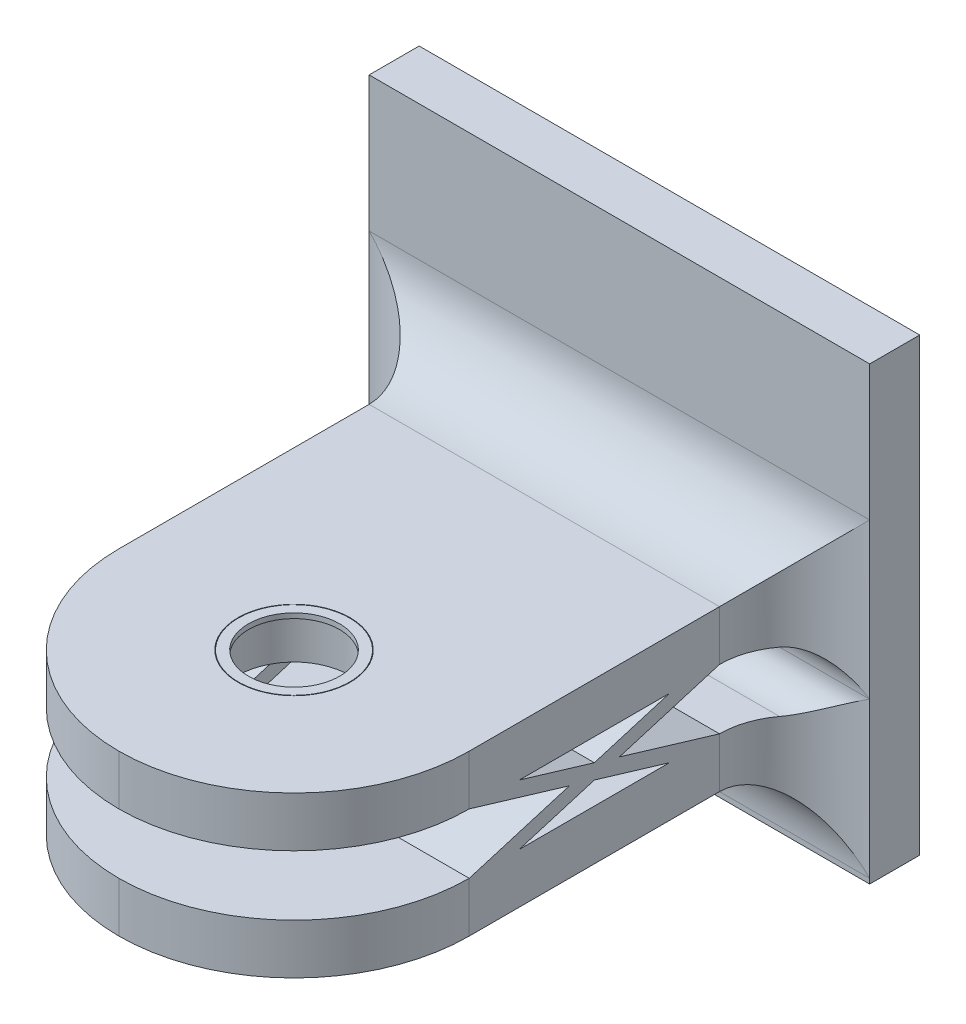
SolidWorks part; units mm, degrees
ref_plane "Plan de face" through (0, 0, 0) normal (1, 0, 0) x (0, 1, 0)
ref_plane "Plan de dessus" through (0, 0, 0) normal (0, 0, 1) x (0, 1, 0)
ref_plane "Plan de droite" through (0, 0, 0) normal (0, 1, 0) x (-1, 0, 0)
sketch "Esquisse1" plane through (0, 0, 0) normal (0, 0, 1) x (0, 1, 0)
  line L1 (0, 0) -> (90, 0)
  line L2 (0, 0) -> (0, 100)
  line L3 (0, 100) -> (90, 100)
  line L4 (90, 0) -> (90, 100)
  dimension "D1" = 90
  dimension "D2" = 100
extrude "Boss.-Extru.1" add sketch "Esquisse1" along normal blind 10
sketch "Esquisse2" plane through (0, 0, 10) normal (0, 0, 1) x (1, 0, 0)
  line L6 (0, 0) -> (0, 90) construction
  line L8 (-85, 48) -> (-15, 48)
  line L9 (-85, 48) -> (-85, 38)
  line L10 (-85, 38) -> (-15, 38)
  line L11 (-15, 48) -> (-15, 38)
  line L16 (-85, 26) -> (-15, 26)
  line L17 (-85, 26) -> (-85, 16)
  line L18 (-85, 16) -> (-15, 16)
  line L19 (-15, 26) -> (-15, 16)
  dimension "D2" = 10
  dimension "D6" = 70
  dimension "D7" = 15
  dimension "D12" = 70
  dimension "D13" = 10
  dimension "D14" = 12
extrude "Boss.-Extru.2" add sketch "Esquisse2" along normal blind 100
fillet "Congé1" radius 35 4 edges at (-15, 43, 110) (-85, 43, 110) (-15, 21, 110) (-85, 21, 110)
sketch "Esquisse3" plane through (0, 90, 0) normal (0, 1, 0) x (-1, 0, 0)
  line L0 (0, 10) -> (0, 0) construction
  line L2 (0, 0) -> (100, 0) construction
  circle A0 centre (50, 75) radius 11.2
  dimension "D3" = 22.4
  dimension "D1" = 50
  dimension "D2" = 75
extrude "Enlèv. mat.-Extru.1" cut sketch "Esquisse3" against normal blind 208
fillet "Congé2" radius 15 6 edges at (-15, 43, 10) (-50, 48, 10) (-85, 43, 10) (-85, 21, 10) (-15, 21, 10) (-50, 16, 10)
ref_axis "Axe2" through (-50, 16, 110) along (0, 0, -1)
sketch "Esquisse10" plane through (0, 48, 0) normal (0, 1, 0) x (-1, 0, 0)
  circle A0 centre (50, 75) radius 11.0955
  circle A1 centre (50, 75) radius 9.0955
  dimension "D1" = 2
extrude "Boss.-Extru.7" add sketch "Esquisse10" against normal blind 1 separate body
fillet "Congé7" radius 6 2 edges at (-50, 26, 10) (-50, 38, 10)
sketch "Esquisse15" plane through (0, 26, 0) normal (0, 1, 0) x (-1, 0, 0)
  circle A0 centre (50, 75) radius 11.0955
  circle A1 centre (50, 75) radius 9.0955
extrude "Boss.-Extru.11" add sketch "Esquisse15" against normal blind 0.5 separate body
sketch "Esquisse16" plane through (-15, 0, 0) normal (1, 0, 0) x (0, 1, 0)
  line L0 (26, 25) -> (26, 35)
  line L1 (26, 25) -> (38, 65)
  line L2 (26, 35) -> (38, 75)
  line L3 (38, 65) -> (38, 75)
  line L4 (26, 75) -> (26, 25) construction
  dimension "D1" = 10
extrude "Boss.-Extru.12" add sketch "Esquisse16" against normal blind 17
sketch "Esquisse17" plane through (-15, 0, 0) normal (1, 0, 0) x (0, 1, 0)
  line L0 (26, 75) -> (26, 65)
  line L1 (26, 75) -> (38, 35)
  line L2 (26, 65) -> (38, 25)
  line L3 (38, 35) -> (38, 25)
  line L4 (26, 75) -> (26, 35) construction
  dimension "D1" = 10
extrude "Boss.-Extru.13" add sketch "Esquisse17" against normal blind 17
ref_plane "Plan1" through (-50, 0, 0) normal (-1, 0, 0) x (0, 0, 1)
mirror "Symétrie1" about plane through (-50, 0, 0) normal (-1, 0, 0) of "Boss.-Extru.13", "Boss.-Extru.12"
